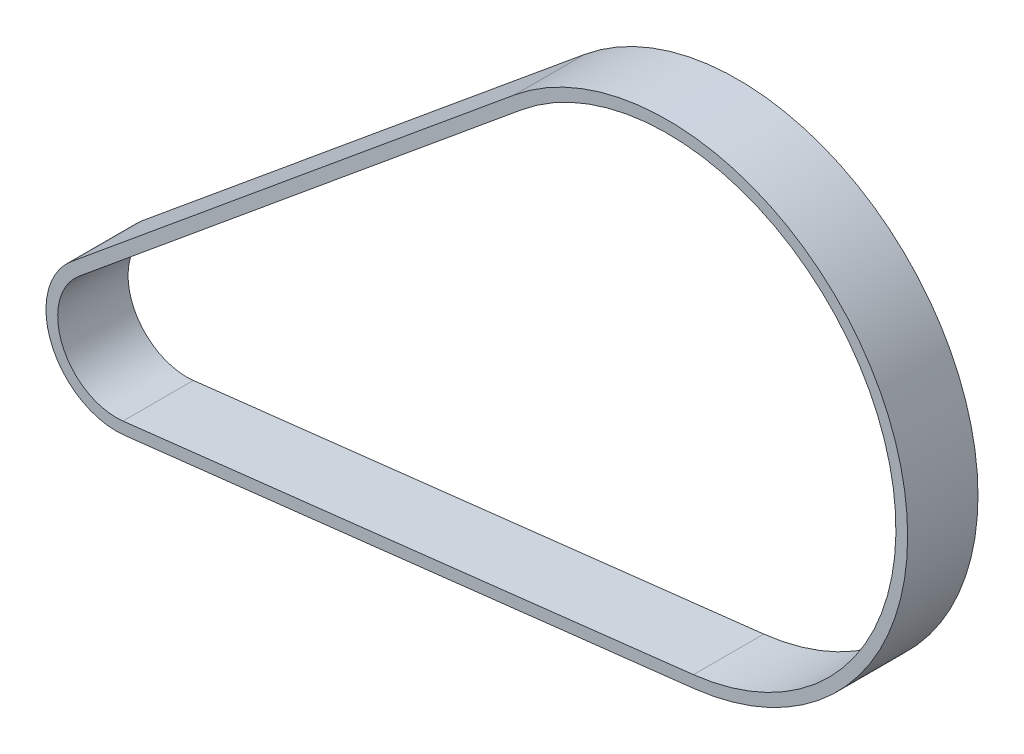
SolidWorks part; units mm, degrees
ref_plane "Front Plane" through (0, 0, 0) normal (0, 0, 1) x (1, 0, 0)
ref_plane "Top Plane" through (0, 0, 0) normal (0, 1, 0) x (1, 0, 0)
ref_plane "Right Plane" through (0, 0, 0) normal (1, 0, 0) x (0, 0, -1)
ref_axis "X" through (-88.99, 0, 0) along (1, 0, 0)
ref_axis "Y" through (0, 55, 0) along (0, -1, 0)
ref_axis "Z" through (0, 0, -88.99) along (0, 0, 1)
sketch "Sketch1" plane through (0, 0, 0) normal (0, 0, 1) x (1, 0, 0)
  line L0 (-3.1833, 3.8557) -> (34.5852, 35.0374)
  line L1 (0.5712, -4.9673) -> (49.2276, 0.6277)
  arc A0 (-3.1833, 3.8557) -> (0.5712, -4.9673) centre (0, 0) ccw
  arc A1 (49.2276, 0.6277) -> (34.5852, 35.0374) centre (47, 20) ccw
  arc A2 (-3.1833, 3.8557) -> (0.5712, -4.9673) centre (0, 0) ccw construction
  arc A3 (49.2276, 0.6277) -> (34.5852, 35.0374) centre (47, 20) ccw construction
extrude "Extrude-Thin1" add sketch "Sketch1" along normal mid plane 6 thin thin type one direction wall 1
